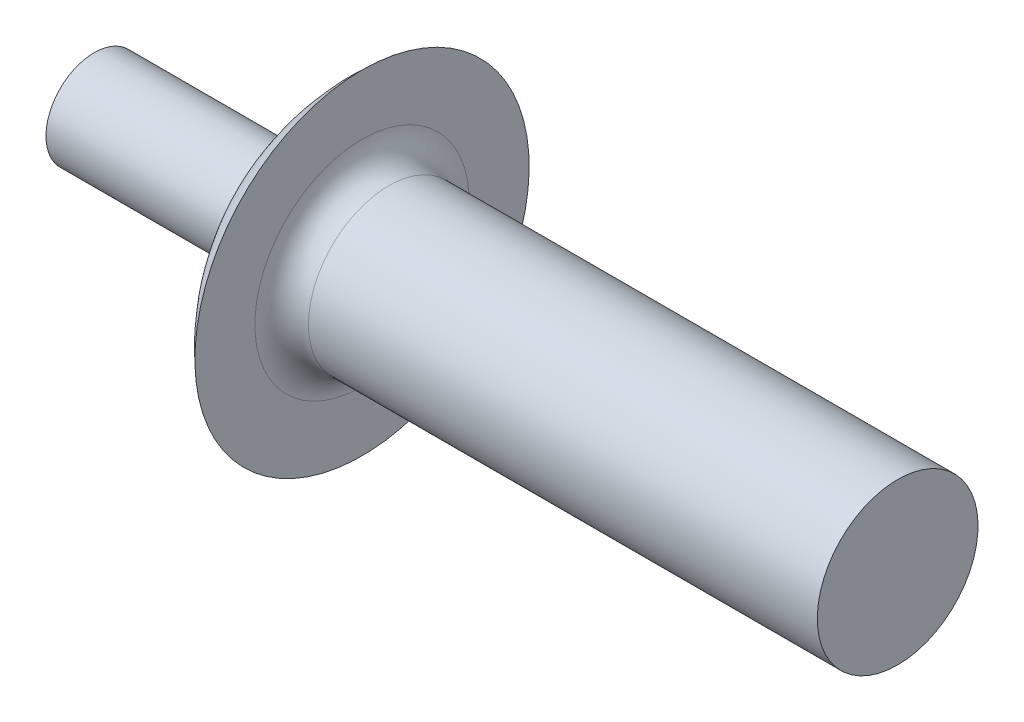
SolidWorks part; units mm, degrees
ref_plane "Front" through (0, 0, 0) normal (0, 0, 1) x (1, 0, 0)
ref_plane "Top" through (0, 0, 0) normal (0, 1, 0) x (1, 0, 0)
ref_plane "Right" through (0, 0, 0) normal (1, 0, 0) x (0, 0, -1)
sketch "Sketch1" plane through (13.2414, 10.1214, 0) normal (0, 0, 1) x (0, 1, 0)
  line L0 (-10.1214, -1.7586) -> (-8.6214, -1.7586)
  line L1 (-8.6214, -1.7586) -> (-8.6214, 8.2414)
  line L2 (-8.6214, 8.2414) -> (-7.0014, 8.2414)
  line L3 (-10.1214, 34.3377) -> (-10.1214, -10.975) construction
  line L4 (-9.2214, 9.5432) -> (-9.2214, 13.2414)
  line L5 (-9.2214, 13.2414) -> (-10.1214, 13.2414)
  line L6 (-10.1214, -1.7586) -> (-10.1214, 13.2414)
  arc A0 (-7.0014, 8.2414) -> (-9.2214, 9.5432) centre (-10.1214, 5.4648) ccw
  dimension "D2" = 5
revolve "Base-Revolve" add sketch "Sketch1" angle 360 about L3
fillet "Fillet1" radius 0.5 1 edges at (5, -1.5, 0)
equation "\"D2@Sketch1\" = \"l@Sketch1\" / 2"
